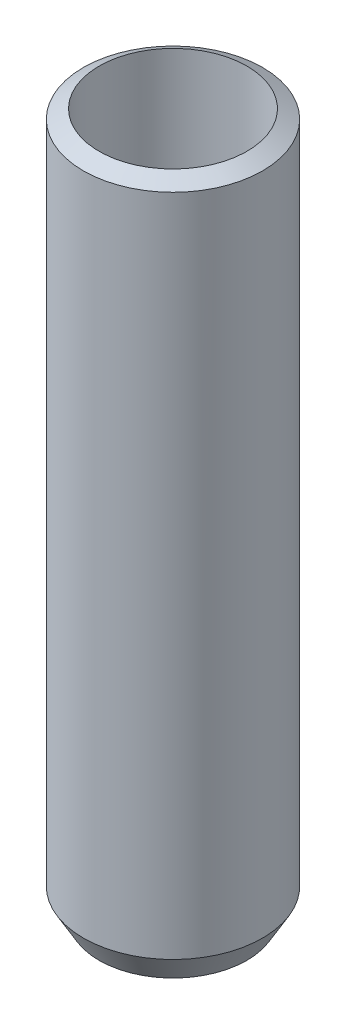
SolidWorks part; units mm, degrees
ref_plane "Front Plane" through (0, 0, 0) normal (0, 0, 1) x (1, 0, 0)
ref_plane "Top Plane" through (0, 0, 0) normal (0, 1, 0) x (1, 0, 0)
ref_plane "Right Plane" through (0, 0, 0) normal (1, 0, 0) x (0, 0, -1)
sketch "Sketch1" plane through (0, 0, 0) normal (0, 1, 0) x (1, 0, 0)
  circle A0 centre (0, 0) radius 25
  dimension "SHAFT_OD" = 50
extrude "Boss-Extrude1" add sketch "Sketch1" along normal blind 198.9417
sketch "Sketch2" plane through (0, 0, 0) normal (0, 1, 0) x (1, 0, 0)
  circle A0 centre (0, 0) radius 20.6207
  dimension "BORE_D" = 41.2415
extrude "Cut-Extrude1" cut sketch "Sketch2" along normal through all
chamfer "Chamfer1" distance 4.9595 angle 60 2 edges at (0, 198.9417, 25) (0, 0, 25) first distance on face at (0, 198.9417, 25) first distance on face at (0, 0, 20.6207)
